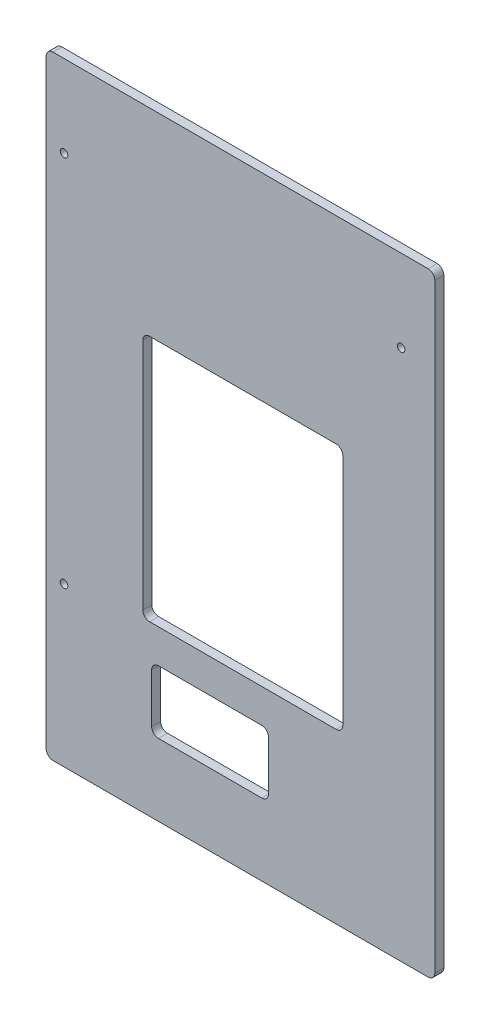
SolidWorks part; units mm, degrees
material "Verre"
ref_plane "Plan de face" through (0, 0, 0) normal (0, 0, 1) x (1, 0, 0)
ref_plane "Plan de dessus" through (0, 0, 0) normal (0, 1, 0) x (1, 0, 0)
ref_plane "Plan de droite" through (0, 0, 0) normal (1, 0, 0) x (0, 0, -1)
sketch "Esquisse1" plane through (0, 0, 0) normal (0, 0, 1) x (1, 0, 0)
  line L1 (0, 0) -> (172.93, 0)
  line L2 (0, 0) -> (0, 273)
  line L3 (0, 273) -> (172.93, 273)
  line L4 (172.93, 0) -> (172.93, 273)
  line L5 (43, 75) -> (132, 75)
  line L6 (43, 75) -> (43, 185)
  line L7 (43, 185) -> (132, 185)
  line L8 (132, 75) -> (132, 185)
  line L9 (46.93, 60) -> (98.93, 60)
  line L10 (46.93, 60) -> (46.93, 32)
  line L11 (46.93, 32) -> (98.93, 32)
  line L12 (98.93, 60) -> (98.93, 32)
  circle A0 centre (7.93, 236.5) radius 1.5
  circle A1 centre (7.93, 70.5) radius 1.5
  circle A2 centre (157.93, 236.5) radius 1.5
  dimension "D8" = 3
  dimension "D10" = 3
  dimension "D14" = 3
  dimension "D1" = 172.93
  dimension "D2" = 273
  dimension "D3" = 43
  dimension "D4" = 89
  dimension "D5" = 110
  dimension "D6" = 15
  dimension "D7" = 7.93
  dimension "D9" = 7.93
  dimension "D11" = 36.5
  dimension "D12" = 70.5
  dimension "D13" = 36.5
  dimension "D15" = 15
  dimension "D16" = 74
  dimension "D17" = 28
  dimension "D18" = 32
  dimension "D19" = 52
extrude "Boss.-Extru.1" add sketch "Esquisse1" along normal blind 4
fillet "Congé1" radius 3 12 edges at (0, 0, 2) (172.93, 0, 2) (172.93, 273, 2) (0, 273, 2) (43, 75, 2) (132, 75, 2) (132, 185, 2) (43, 185, 2) (98.93, 32, 2) (46.93, 32, 2) (98.93, 60, 2) (46.93, 60, 2)
hole_wizard "Dégagement M31" positions "Esquisse2" profile "Esquisse3" hole size "M3" standard "ISO" end condition through all
sketch "Esquisse2" plane through (0, 0, 4) normal (0, 0, 1) x (1, 0, 0)
  point P0 (7.93, 236.5)
  point P3 (7.93, 70.5)
  point P6 (157.93, 236.5)
sketch "Esquisse3" plane through (7.93, 236.5, 4) normal (1, 0, 0) x (0, -1, 0)
  line L0 (0, 0) -> (0, 4)
  line L1 (0, 4) -> (1.7, 4)
  line L2 (1.7, 4) -> (1.7, 0)
  line L5 (1.7, 0) -> (0, 0)
  line L11 (0, -6.35) -> (0, 107.95) construction
  dimension "Diamètre du perçage jusqu'au prochain" = 3.4
  dimension "Profondeur du perçage jusqu'au prochain" = 4
